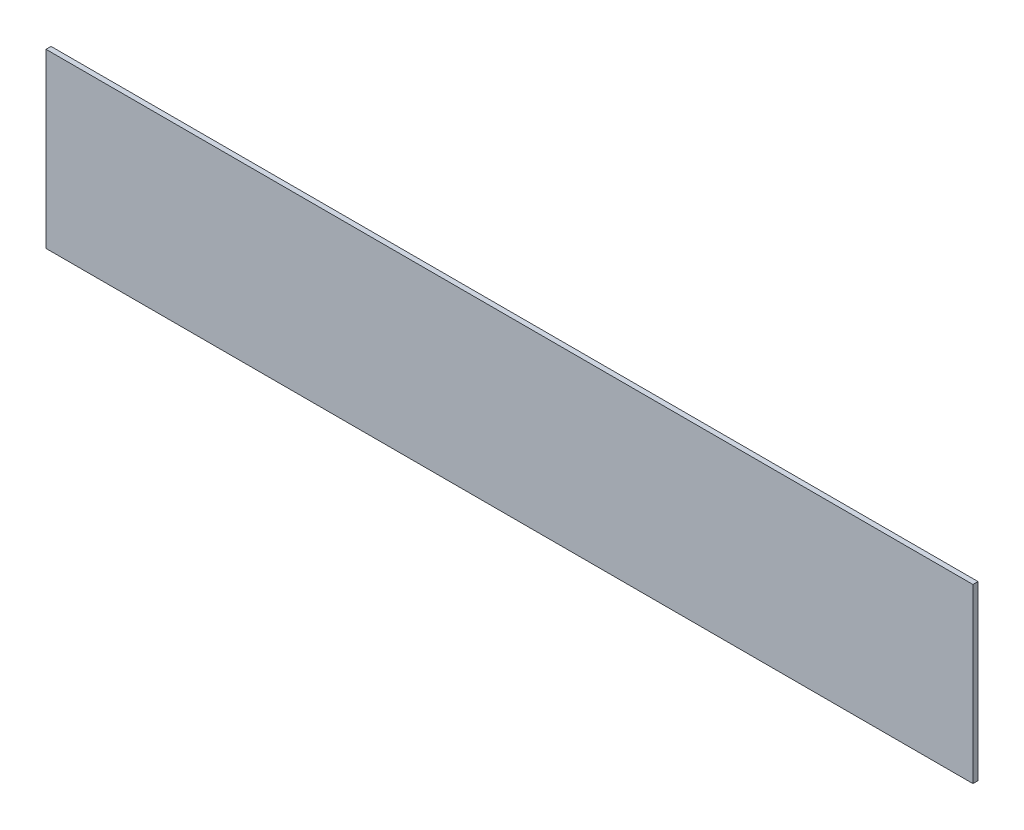
SolidWorks part; units mm, degrees
ref_plane "Front Plane" through (0, 0, 0) normal (0, 0, 1) x (1, 0, 0)
ref_plane "Top Plane" through (0, 0, 0) normal (0, 1, 0) x (1, 0, 0)
ref_plane "Right Plane" through (0, 0, 0) normal (1, 0, 0) x (0, 0, -1)
sketch "Sketch2" plane through (0, 0, 0) normal (0, 0, 1) x (1, 0, 0)
  line L1 (146.5, -27.26) -> (-146.5, -27.26)
  line L2 (146.5, -27.26) -> (146.5, 27.26)
  line L3 (146.5, 27.26) -> (-146.5, 27.26)
  line L4 (-146.5, -27.26) -> (-146.5, 27.26)
  line L5 (146.5, -27.26) -> (-146.5, 27.26) construction
  line L6 (146.5, 27.26) -> (-146.5, -27.26) construction
  point P0 (0, 0)
  dimension "D1" = 293
  dimension "D2" = 54.52
extrude "Boss-Extrude1" add sketch "Sketch2" along normal blind 1.6
